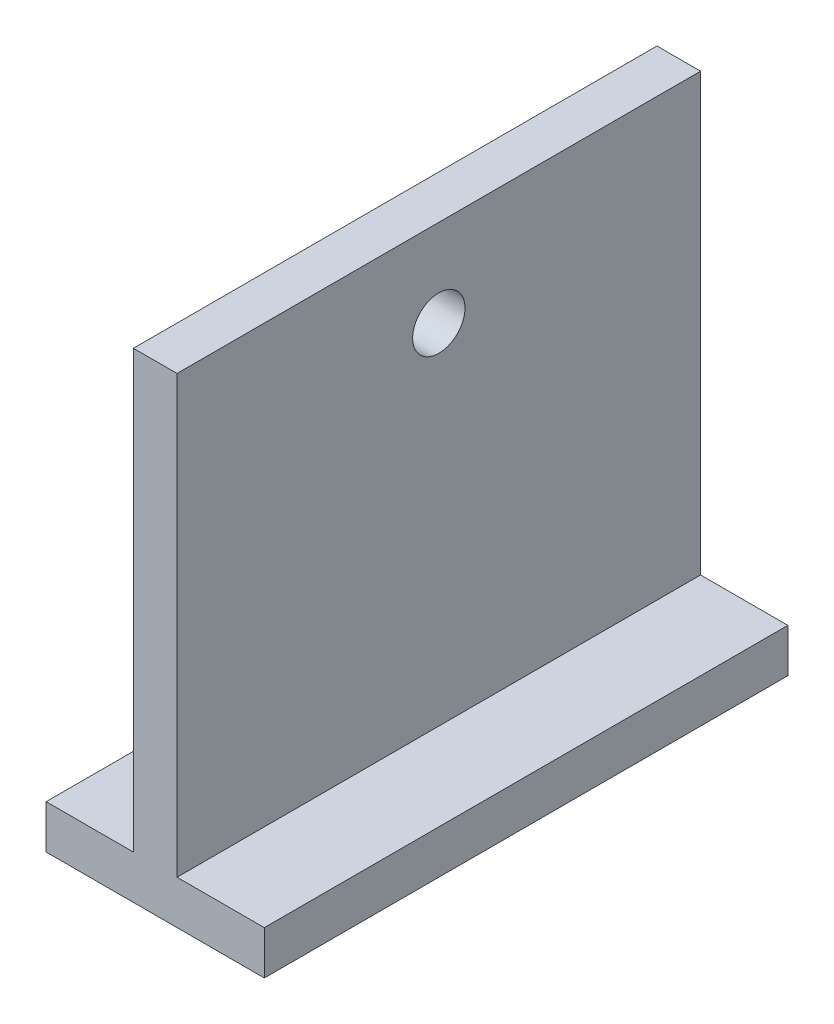
SolidWorks part; units mm, degrees
ref_plane "Front Plane" through (0, 0, 0) normal (0, 0, 1) x (1, 0, 0)
ref_plane "Top Plane" through (0, 0, 0) normal (0, 1, 0) x (1, 0, 0)
ref_plane "Right Plane" through (0, 0, 0) normal (1, 0, 0) x (0, 0, -1)
sketch "Sketch1" plane through (0, 0, 0) normal (0, 0, 1) x (1, 0, 0)
  line L0 (25, 0) -> (25, 5)
  line L1 (0, 0) -> (25, 0)
  line L2 (0, 0) -> (0, 5)
  line L3 (0, 5) -> (10, 5)
  line L4 (12.5, 0) -> (12.5, 9.8976) construction
  line L6 (12.5, 9.8976) -> (12.5, 55) construction
  line L7 (15, 55) -> (10, 55)
  line L8 (10, 5) -> (10, 55)
  line L9 (25, 5) -> (15, 5)
  line L10 (15, 5) -> (15, 55)
  dimension "D1" = 5
  dimension "D2" = 5
  dimension "D3" = 50
  dimension "D4" = 25
extrude "Boss-Extrude1" add sketch "Sketch1" along normal blind 60
sketch "Sketch2" plane through (15, 0, 0) normal (1, 0, 0) x (0, 0, -1)
  line L4 (0, 5) -> (0, 55)
  line L5 (0, 55) -> (-60, 55)
  line L6 (-60, 55) -> (-60, 5)
  line L7 (-60, 5) -> (0, 5)
  line L8 (0, 5) -> (0, 55) construction
  line L9 (0, 55) -> (-60, 55) construction
  line L10 (-60, 55) -> (-60, 5) construction
  line L11 (-60, 5) -> (0, 5) construction
  line L12 (0, 0) -> (0, 5)
  line L13 (0, 5) -> (-60, 5)
  line L14 (-60, 5) -> (-60, 0)
  line L15 (-60, 0) -> (0, 0)
  line L16 (0, 0) -> (0, 5) construction
  line L17 (0, 5) -> (-60, 5) construction
  line L18 (-60, 5) -> (-60, 0) construction
  line L19 (-60, 0) -> (0, 0) construction
  circle A0 centre (-30, 45) radius 3
  point P2 (-30, 55)
  point P4 (-60, 30)
  point P6 (-30, 45)
  point P10 (0, 0)
  point P11 (-30, 45)
  dimension "D4" = 6
  dimension "D2" = 0
  dimension "D3" = 45
  dimension "D1" = 0
extrude "Cut-Extrude1" cut sketch "Sketch2" against normal through all
